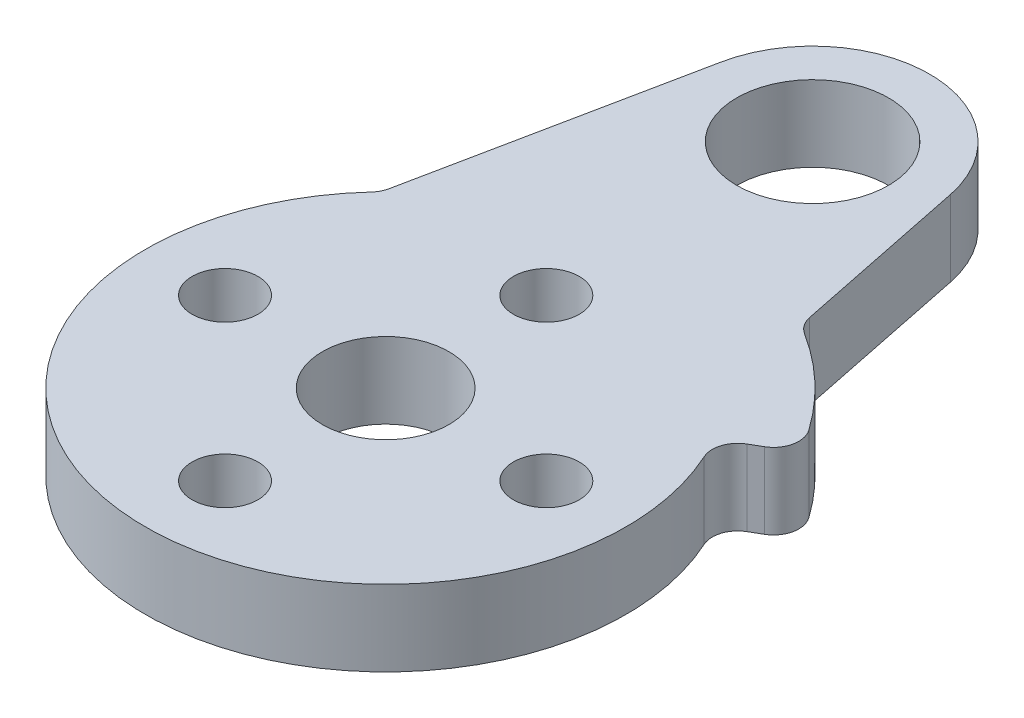
SolidWorks part; units mm, degrees
ref_plane "Front Plane" through (0, 0, 0) normal (0, 0, 1) x (1, 0, 0)
ref_plane "Top Plane" through (0, 0, 0) normal (0, 1, 0) x (1, 0, 0)
ref_plane "Right Plane" through (0, 0, 0) normal (1, 0, 0) x (0, 0, -1)
sketch "Sketch1" plane through (0, 0, 0) normal (0, 1, 0) x (1, 0, 0)
  line L1 (-4.5316, 17.7996) -> (-7.8384, 1.6)
  line L2 (4.5316, 17.7996) -> (7.8384, 1.6)
  arc A0 (-7.8384, 1.6) -> (7.8384, 1.6) centre (0, 0) ccw
  arc A1 (4.5316, 17.7996) -> (-4.5316, 17.7996) centre (0, 16.8746) ccw
  circle A2 centre (0, 16.8746) radius 3
  circle A3 centre (0, 0) radius 2.5
extrude "Boss-Extrude1" add sketch "Sketch1" along normal blind 3
sketch "Sketch2" plane through (0, 3, 0) normal (0, 1, 0) x (1, 0, 0)
  line L0 (0, 0) -> (0, 6.35) construction
  circle A0 centre (0, 6.35) radius 1.3
  circle A1 centre (6.35, 0) radius 1.3
  circle A2 centre (0, -6.35) radius 1.3
  circle A3 centre (-6.35, 0) radius 1.3
  point P13 (0, 0)
  dimension "D1" = 4
extrude "Cut-Extrude1" cut sketch "Sketch2" against normal blind 3
sketch "Sketch3" plane through (0, 3, 0) normal (0, 1, 0) x (1, 0, 0)
  line L0 (-7.8384, 1.6) -> (-6.8137, 6.62)
  line L1 (6.8137, 6.62) -> (7.8384, 1.6)
  line L2 (7.8384, 1.6) -> (4.5316, 17.7996) construction
  arc A1 (-6.8137, 6.62) -> (6.8137, 6.62) centre (0, 0) ccw
  arc A2 (-7.8384, 1.6) -> (7.8384, 1.6) centre (0, 0) ccw construction
  arc A3 (-7.8384, 1.6) -> (7.8384, 1.6) centre (0, 0) ccw
extrude "Boss-Extrude2" add sketch "Sketch3" against normal blind 3
sketch "Sketch4" plane through (0, 3, 0) normal (0, 1, 0) x (1, 0, 0)
  line L1 (8.2272, 4.75) -> (10.3923, 6)
  line L2 (0, 12) -> (0, 9.5)
  arc A0 (10.3923, 6) -> (0, 12) centre (0, 0) ccw
  arc A1 (8.2272, 4.75) -> (0, 9.5) centre (0, 0) ccw
extrude "Boss-Extrude3" add sketch "Sketch4" against normal up to surface (3 mm away) up to face at (0, 0, -9.1048)
fillet "Fillet1" radius 1 4 edges at (6.0495, 1.5, -10.3636) (8.2272, 1.5, -4.75) (10.3923, 1.5, -6) (-6.8137, 1.5, -6.62)
